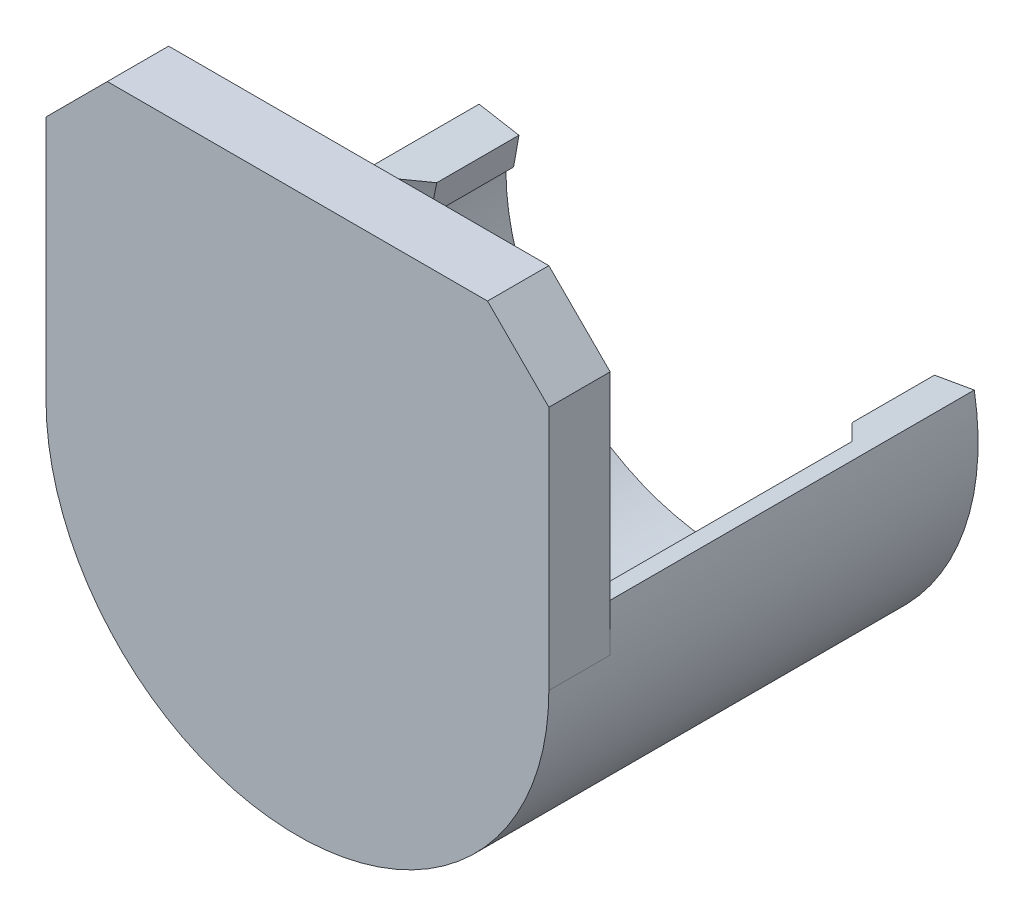
SolidWorks part; units mm, degrees
material "PET"
ref_plane "Front Plane" through (0, 0, 0) normal (0, 0, 1) x (1, 0, 0)
ref_plane "Top Plane" through (0, 0, 0) normal (0, 1, 0) x (1, 0, 0)
ref_plane "Right Plane" through (0, 0, 0) normal (1, 0, 0) x (0, 0, -1)
sketch "Sketch1" plane through (0, 0, 0) normal (0, 0, 1) x (1, 0, 0)
  line L0 (0, 0) -> (-11.2564, 1.9848) construction
  line L1 (-11.2564, 1.9848) -> (-12.8197, 2.2605)
  line L2 (0, 0) -> (0, -13.0175) construction
  line L3 (11.2564, 1.9848) -> (12.8197, 2.2605)
  line L4 (-11.2564, 1.9848) -> (-10.7561, 1.8966)
  line L5 (-10.7561, 1.8966) -> (-11.0317, 0.3332)
  line L6 (-11.0317, 0.3332) -> (-11.43, 0)
  line L7 (11.0317, 0.3332) -> (11.43, 0)
  line L8 (10.7561, 1.8966) -> (11.0317, 0.3332)
  line L9 (11.2564, 1.9848) -> (10.7561, 1.8966)
  arc A0 (-11.43, 0) -> (11.43, 0) centre (0, 0) ccw
  arc A1 (-12.8197, 2.2605) -> (12.8197, 2.2605) centre (0, 0) ccw
  arc A2 (11.2564, 1.9848) -> (-11.2564, 1.9848) centre (0, 0) ccw construction
  arc A3 (12.8197, 2.2605) -> (-12.8197, 2.2605) centre (0, 0) ccw construction
  dimension "D1" = 22.86
  dimension "D2" = 1.5875
  dimension "D3" = 100
  dimension "D4" = 0.508
  dimension "D5" = 1.5875
extrude "Boss-Extrude1" add sketch "Sketch1" along normal blind 19.05
sketch "Sketch3" plane through (0, 0, 19.05) normal (0, 0, 1) x (1, 0, 0)
  circle A0 centre (0, 0) radius 13.0175
extrude "Boss-Extrude2" add sketch "Sketch3" along normal blind 3.175
sketch "Sketch4" plane through (0, 0, 19.05) normal (0, 0, -1) x (-1, 0, 0)
  circle A0 centre (0, 0) radius 11.43
extrude "Cut-Extrude1" cut sketch "Sketch4" along normal offset from surface (15.875 mm away) 3.175 up to face at (0, -2.2159, 0)
chamfer "Chamfer1" distance 1.5875 angle 45 2 edges at (11.3865, 0.9962, 3.175) (-11.3865, 0.9962, 3.175)
chamfer "Chamfer2" distance 0.5292 angle 45 2 edges at (11.2564, 1.9848, 11.9063) (-11.2564, 1.9848, 11.9063)
sketch "Sketch5" plane through (0, 0, 22.225) normal (0, 0, 1) x (1, 0, 0)
  line L1 (13.0175, 0) -> (-13.0175, 0)
  line L2 (13.0175, 0) -> (13.0175, 15.875)
  line L3 (13.0175, 15.875) -> (-13.0175, 15.875)
  line L4 (-13.0175, 0) -> (-13.0175, 15.875)
  circle A0 centre (0, 0) radius 13.0175 construction
  point P6 (-13.0175, 0)
  point P7 (-12.9918, -0.8179)
  dimension "D1" = 15.875
extrude "Boss-Extrude3" add sketch "Sketch5" against normal up to surface (3.175 mm away) up to face at (0, 1.575, 19.05)
chamfer "Chamfer3" distance 3.175 angle 45 2 edges at (-13.0175, 15.875, 20.6375) (13.0175, 15.875, 20.6375)
